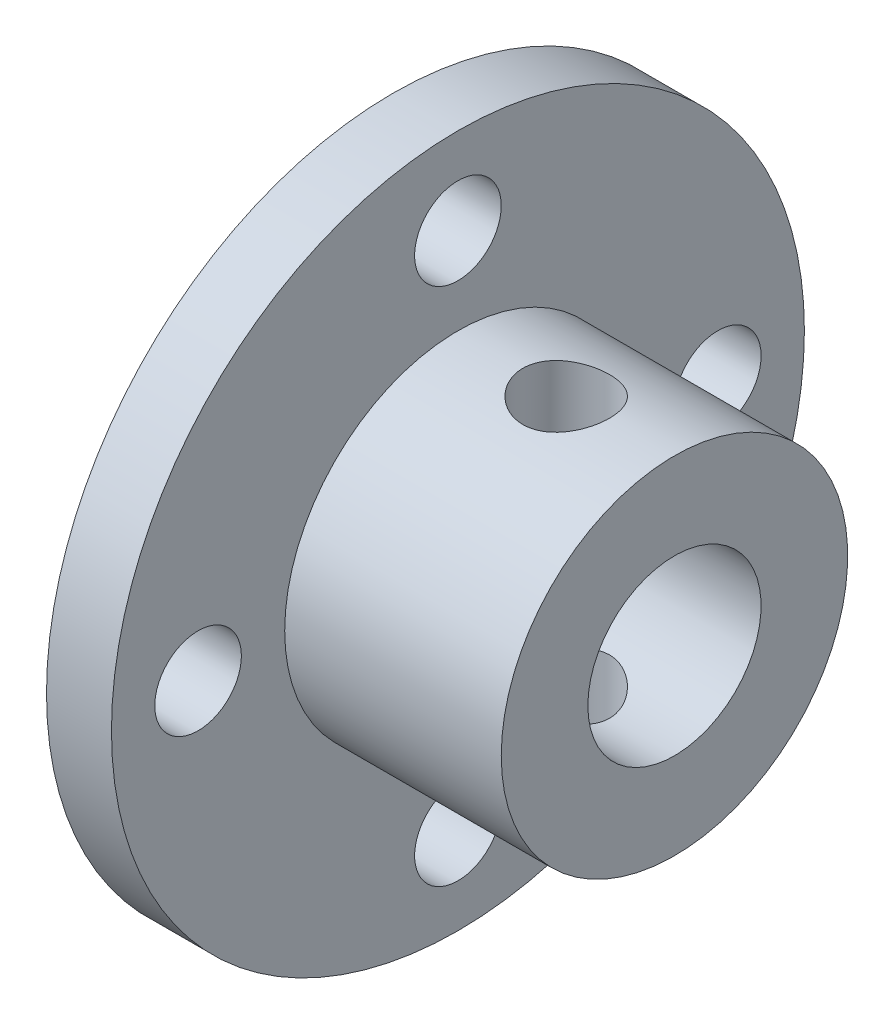
SolidWorks part; units mm, degrees
ref_plane "前视基准面" through (0, 0, 0) normal (0, 0, 1) x (1, 0, 0)
ref_plane "上视基准面" through (0, 0, 0) normal (0, 1, 0) x (1, 0, 0)
ref_plane "右视基准面" through (0, 0, 0) normal (1, 0, 0) x (0, 0, -1)
sketch "草图1" plane through (0, 0, 0) normal (0, 1, 0) x (1, 0, 0)
  line L0 (0, 0) -> (0, 4) construction
  line L1 (0, 16) -> (3, 16)
  line L2 (3, 16) -> (3, 8)
  line L3 (3, 8) -> (13, 8)
  line L4 (13, 8) -> (13, 4)
  line L5 (13, 4) -> (0, 4)
  line L6 (0, 16) -> (0, 4)
  line L7 (0, 0) -> (4.9154, 0) construction
  dimension "D1" = 4
  dimension "D2" = 13
  dimension "D3" = 3
  dimension "D4" = 4
  dimension "D5" = 16
revolve "旋转1" add sketch "草图1" angle 360 about L7
sketch "草图2" plane through (3, 0, 0) normal (1, 0, 0) x (0, 0, -1)
  line L0 (0, 0) -> (12, 0) construction
  circle A0 centre (0, 0) radius 12 construction
  circle A1 centre (12, 0) radius 2
  circle A2 centre (0, -12) radius 2
  circle A3 centre (-12, 0) radius 2
  circle A4 centre (0, 12) radius 2
  point P14 (0, 0)
  dimension "D1" = 24
  dimension "D2" = 4
  dimension "D3" = 4
extrude "切除-拉伸1" cut sketch "草图2" against normal blind 10
sketch "草图3" plane through (0, 0, 0) normal (0, 1, 0) x (1, 0, 0)
  line L0 (13, 0) -> (8, 0) construction
  line L1 (13, -8) -> (13, 8) construction
  circle A0 centre (8, 0) radius 2
  dimension "D1" = 4
  dimension "D2" = 5
extrude "切除-拉伸2" cut sketch "草图3" against normal blind 10 and the other way blind 10
